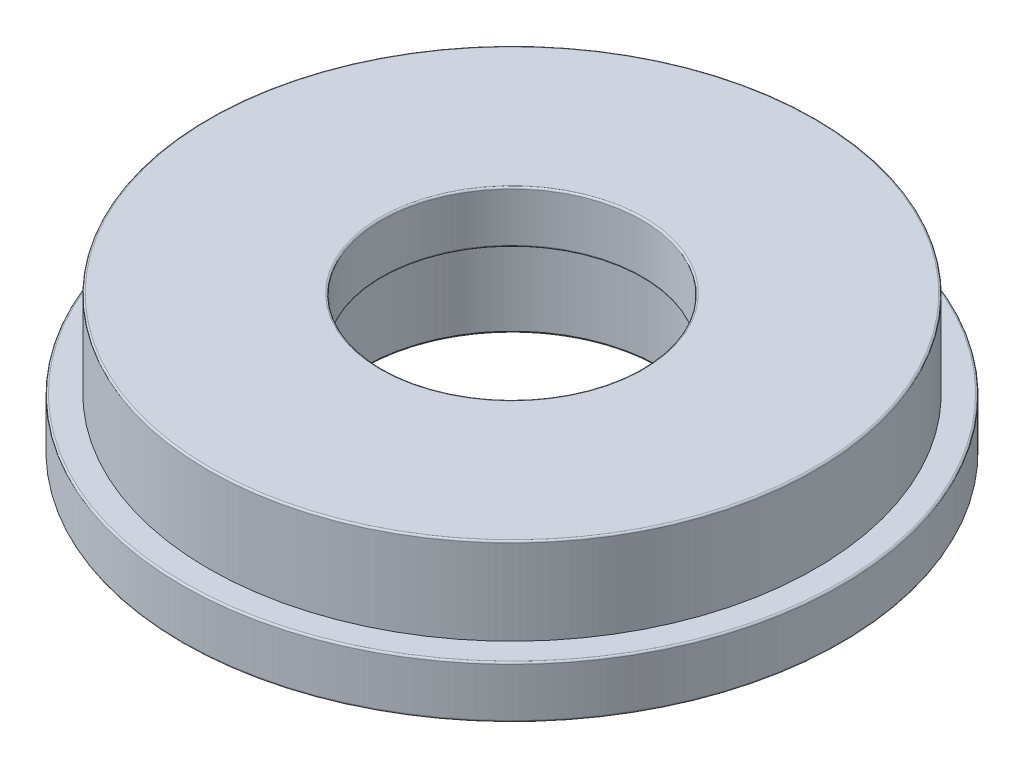
SolidWorks part; units mm, degrees
ref_plane "前视基准面" through (0, 0, 0) normal (0, 0, 1) x (1, 0, 0)
ref_plane "上视基准面" through (0, 0, 0) normal (0, 1, 0) x (1, 0, 0)
ref_plane "右视基准面" through (0, 0, 0) normal (1, 0, 0) x (0, 0, -1)
other "Configuration Table"
sketch "草图1" plane through (0, 0, 0) normal (0, 1, 0) x (1, 0, 0)
  circle A0 centre (0, 0) radius 19
  circle A1 centre (0, 0) radius 15 construction
  circle A2 centre (0, 15) radius 3.05
  circle A3 centre (12.9904, 7.5) radius 3.05
  circle A4 centre (12.9904, -7.5) radius 3.05
  circle A5 centre (0, -15) radius 3.05
  circle A6 centre (-12.9904, -7.5) radius 3.05
  circle A7 centre (-12.9904, 7.5) radius 3.05
  point P18 (0, 0)
  dimension "D1" = 6.1
  dimension "D2" = 38
  dimension "D3" = 30
  dimension "D4" = 6
extrude "凸台-拉伸1" add sketch "草图1" along normal blind 3 contours A0
extrude "切除-拉伸1" cut sketch "草图1<3>" along normal blind 1.7 contours A7 | A6 | A5 | A4 | A3 | A2 region at (0, 0, -15) region at (12.9904, 0, -7.5) region at (12.9904, 0, 7.5) region at (0, 0, 15) region at (-12.9904, 0, 7.5) region at (-12.9904, 0, -7.5)
sketch "草图1<3>" plane through (0, 0, 0) normal (0, 1, 0) x (1, 0, 0) same geometry as "草图1"
sketch "草图5" plane through (0, 3, 0) normal (0, 1, 0) x (1, 0, 0)
  circle A0 centre (0, 0) radius 7.5
  circle A1 centre (0, 0) radius 17.5
  dimension "D1" = 35
  dimension "D2" = 15
extrude "凸台-拉伸3" add sketch "草图5" along normal blind 5
sketch "草图8" plane through (0, 0, 0) normal (0, -1, 0) x (1, 0, 0)
  circle A0 centre (0, 0) radius 8.5
  dimension "D1" = 17
extrude "切除-拉伸4" cut sketch "草图8" against normal offset from surface (5 mm away) 3 up to face at (0, 8, 17.5)
fillet "圆角1" radius 0.1 12 edges at (0, 5, 7.5) (-12.9904, 0, -4.45) (-12.9904, 0, 10.55) (0, 0, 18.05) (12.9904, 0, 10.55) (12.9904, 0, -4.45) (0, 0, -11.95) (0, 0, -8.5) (0, 8, 7.5) (0, 8, 17.5) (0, 0, 19) (0, 3, 19)
